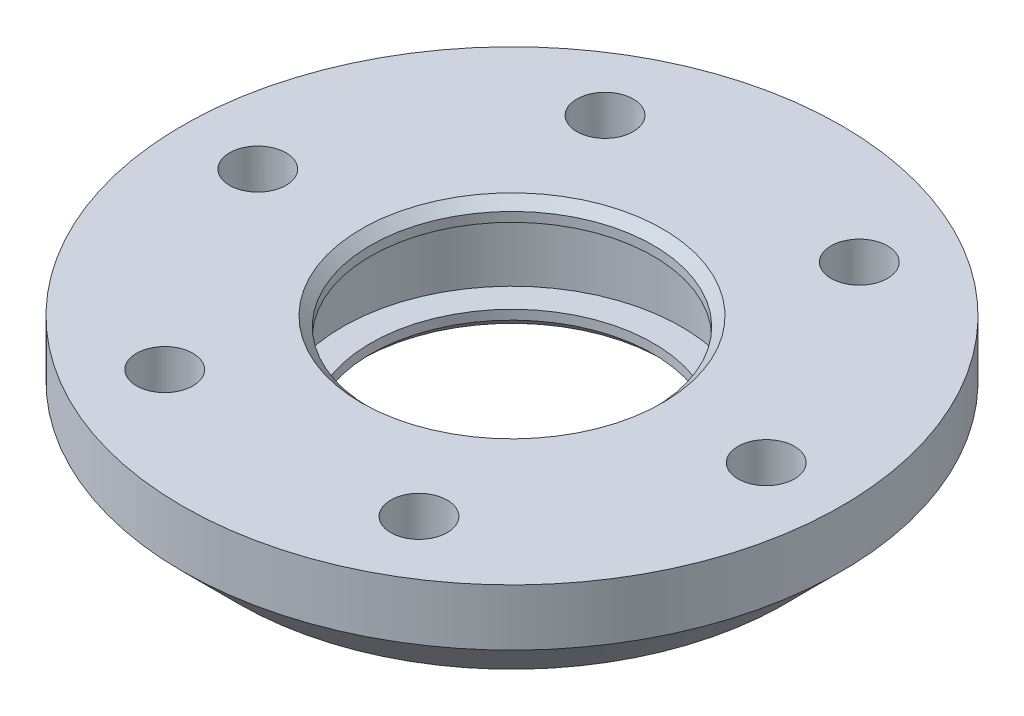
SolidWorks part; units mm, degrees
ref_plane "Front Plane" through (0, 0, 0) normal (0, 0, 1) x (1, 0, 0)
ref_plane "Top Plane" through (0, 0, 0) normal (0, 1, 0) x (1, 0, 0)
ref_plane "Right Plane" through (0, 0, 0) normal (1, 0, 0) x (0, 0, -1)
sketch "Sketch1" plane through (0, 0, 0) normal (0, 1, 0) x (1, 0, 0)
  circle A0 centre (0, 0) radius 13.5 construction
  circle A1 centre (13.5, 0) radius 1.5
  circle A2 centre (6.75, -11.6913) radius 1.5
  circle A3 centre (-6.75, -11.6913) radius 1.5
  circle A4 centre (-13.5, 0) radius 1.5
  circle A5 centre (-6.75, 11.6913) radius 1.5
  circle A6 centre (6.75, 11.6913) radius 1.5
  circle A7 centre (0, 0) radius 17.5
  circle A8 centre (0, 0) radius 7.5
  point P17 (0, 0)
  dimension "D1" = 27
  dimension "D2" = 3
  dimension "D4" = 35
  dimension "D5" = 15
  dimension "D3" = 6
extrude "Boss-Extrude1" add sketch "Sketch1" along normal mid plane 6
sketch "Sketch2" plane through (0, 0, 0) normal (0, 1, 0) x (1, 0, 0)
  circle A0 centre (0, 0) radius 9
  dimension "D1" = 18
extrude "Cut-Extrude1" cut sketch "Sketch2" against normal mid plane 4
sketch "Sketch3" plane through (0, -3, 0) normal (0, -1, 0) x (1, 0, 0)
  circle A0 centre (0, 0) radius 12
  circle A1 centre (0, 0) radius 15
  circle A2 centre (-13.5, 0) radius 1.5 construction
extrude "Boss-Extrude2" add sketch "Sketch3" against normal blind 1.5
chamfer "Chamfer1" distance 0.5 angle 45 2 edges at (0, -3, 7.5) (0, 3, 7.5)
sketch "Sketch4" [suppressed] plane through (0, 4.5, 0) normal (0, 1, 0) x (1, 0, 0)
  circle A0 centre (0, 0) radius 18.5
  circle A1 centre (0, 0) radius 17.5 construction
  circle A2 centre (0, 0) radius 17.5
  dimension "D1" = 1
extrude "Boss-Extrude3" [suppressed] add sketch "Sketch4" against normal blind 2
sketch "Sketch5" [suppressed] plane through (0, -4.5, 0) normal (0, -1, 0) x (-1, 0, 0)
  line L0 (0, 0) -> (-10.8253, -6.25) construction
  line L1 (0, 0) -> (-12.5, 0) construction
  circle A0 centre (0, 0) radius 12.5 construction
  circle A1 centre (-10.8253, -6.25) radius 2.35
  circle A2 centre (-10.8253, 6.25) radius 2.35
  circle A3 centre (0, 12.5) radius 2.35
  circle A4 centre (10.8253, 6.25) radius 2.35
  circle A5 centre (10.8253, -6.25) radius 2.35
  circle A6 centre (0, -12.5) radius 2.35
  point P18 (0, 0)
  dimension "D1" = 4.7
  dimension "D2" = 25
  dimension "D3" = 30
  dimension "D4" = 6
extrude "Cut-Extrude2" [suppressed] cut sketch "Sketch5" against normal blind 4
chamfer "Chamfer2" distance 3 angle 45 1 edges at (0, -3, 17.5)
equation "\"D5@Sketch1\"=18-3"
